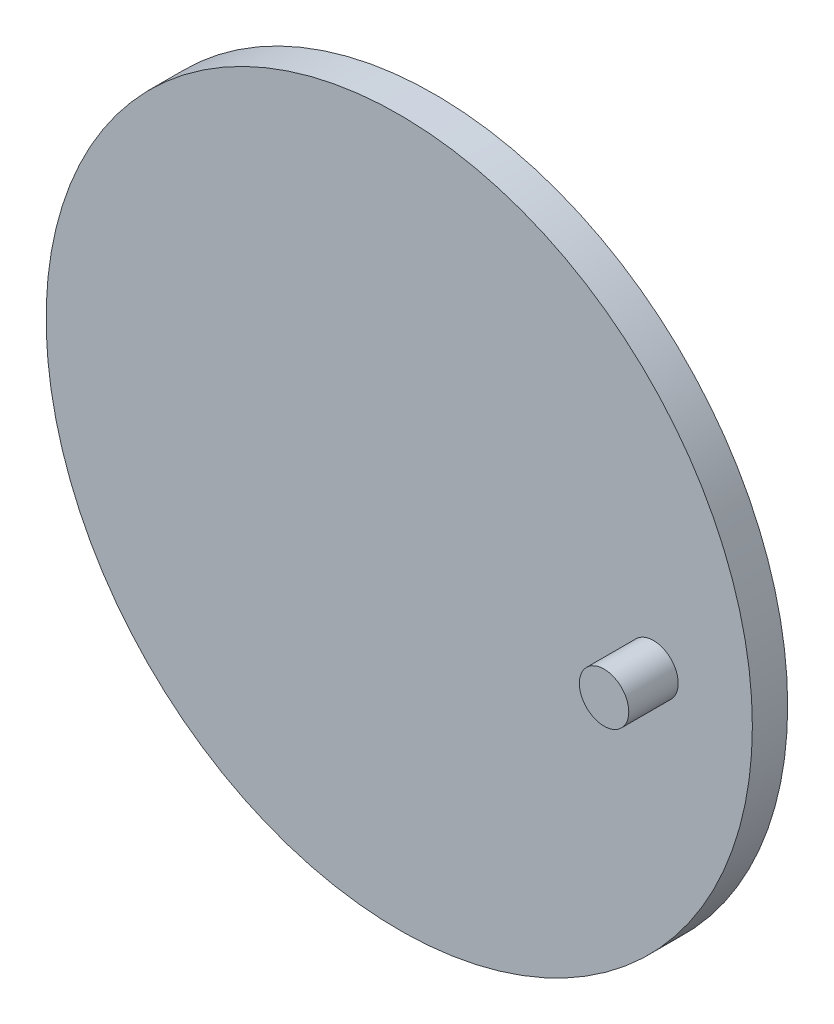
SolidWorks part; units mm, degrees
ref_plane "Front Plane" through (0, 0, 0) normal (0, 0, 1) x (1, 0, 0)
ref_plane "Top Plane" through (0, 0, 0) normal (0, 1, 0) x (1, 0, 0)
ref_plane "Right Plane" through (0, 0, 0) normal (1, 0, 0) x (0, 0, -1)
sketch "Sketch1" plane through (0, 0, 0) normal (0, 0, 1) x (1, 0, 0)
  circle A0 centre (0, 0) radius 63.5
  circle A1 centre (0, 0) radius 4.445
  dimension "D1" = 127
  dimension "D2" = 8.89
extrude "Boss-Extrude1" add sketch "Sketch1" along normal blind 6.35 contours A0 A1 | A1 region at (-61.7039, 0, 0)
sketch "Sketch2" plane through (0, 0, 6.35) normal (0, 0, 1) x (1, 0, 0)
  circle A0 centre (45.72, 0) radius 4.445
  dimension "D1" = 8.89
  dimension "D2" = 45.72
extrude "Boss-Extrude2" add sketch "Sketch2" along normal blind 8.89
extrude "Boss-Extrude3" add sketch "Sketch1<3>" against normal blind 6.35 contours A1 region at (0, 0, 0)
sketch "Sketch1<3>" plane through (0, 0, 0) normal (0, 0, 1) x (1, 0, 0) same geometry as "Sketch1"
sketch "Sketch3" plane through (0, 0, -6.35) normal (0, 0, -1) x (-1, 0, 0)
  circle A0 centre (0, 0) radius 7.6652
  dimension "D1" = 15.3305
extrude "Boss-Extrude4" add sketch "Sketch3" along normal blind 2.54
